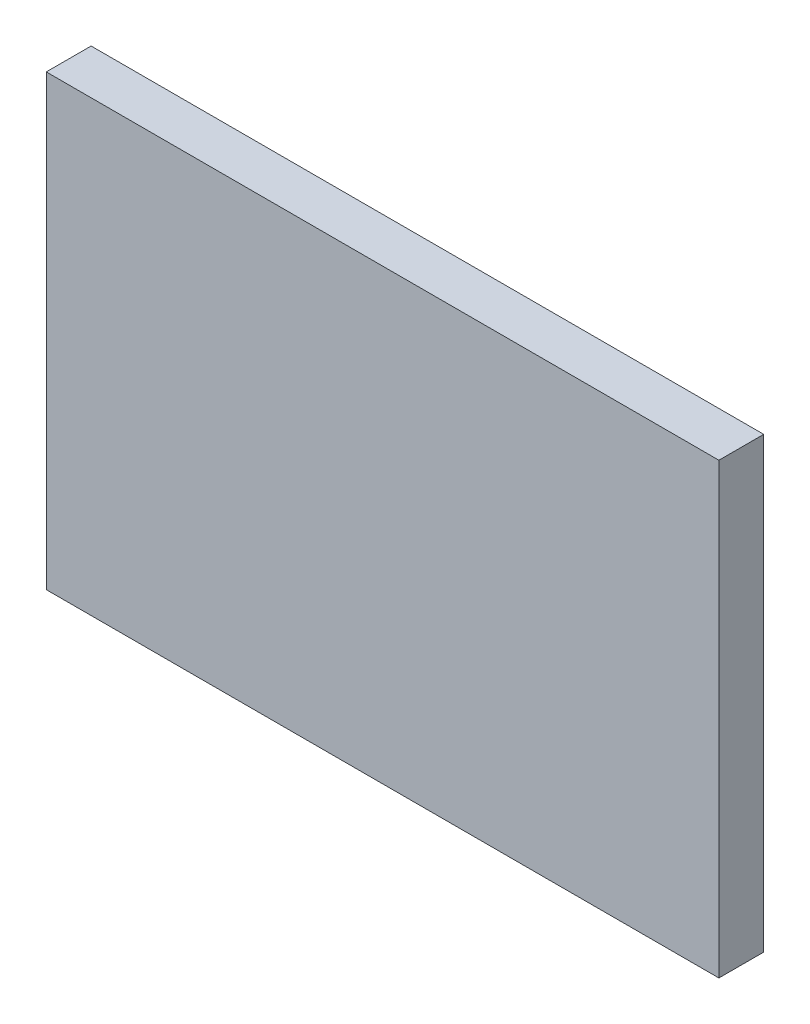
SolidWorks part; units mm, degrees
ref_plane "Ebene vorne" through (0, 0, 0) normal (0, 0, 1) x (1, 0, 0)
ref_plane "Ebene oben" through (0, 0, 0) normal (0, 1, 0) x (1, 0, 0)
ref_plane "Ebene rechts" through (0, 0, 0) normal (1, 0, 0) x (0, 0, -1)
other "Massenmittelpunkt"
sketch "Skizze1" plane through (0, 0, 0) normal (0, 0, 1) x (1, 0, 0)
  line L0 (-15, 10) -> (-15, -10)
  line L1 (-15, -10) -> (15, -10)
  line L2 (15, -10) -> (15, 10)
  line L3 (15, 10) -> (-15, 10)
  line L4 (-15, 0) -> (15, 0) construction
  line L5 (0, 10) -> (0, -10) construction
  point P3 (0, 10)
  point P5 (15, 0)
  point P6 (0, -10)
  point P7 (-15, 0)
  point P12 (0, 0)
  dimension "D1" = 30
  dimension "D2" = 30
  dimension "D3" = 20
  dimension "D4" = 20
  dimension "D5" = 90
ref_axis "Achse1" through (11, 0, 0) along (-1, 0, 0)
ref_plane "Rotation_Plane" through (0, 0, 0) normal (0, 0, -1) x (-1, 0, 0)
ref_plane "Top_Plane" through (0, 0, 2) normal (0, 0, -1) x (-1, 0, 0)
sketch "Skizze2" plane through (0, 0, 2) normal (0, 0, -1) x (-1, 0, 0)
  line L0 (15, 10) -> (15, -10)
  line L1 (15, -10) -> (-15, -10)
  line L2 (-15, -10) -> (-15, 10)
  line L3 (-15, 10) -> (15, 10)
  line L4 (0, 10) -> (0, -10) construction
  line L5 (15, 0) -> (-15, 0) construction
  line L6 (0, 10) -> (0, -10) construction
  line L7 (0, 10) -> (0, -10) construction
  point P0 (0, 0)
  point P6 (0, 10)
  point P7 (-15, 0)
  point P8 (0, -10)
  point P9 (15, 0)
  point P14 (0, 0)
  dimension "D5" = 90
  dimension "D1" = 20
  dimension "D2" = 20
  dimension "D3" = 30
  dimension "D4" = 30
  dimension "D6" = 0
loft "Ausformung2" add profiles "Skizze1", "Skizze2" connector at (-15, -10, 0) connector at (-15, -10, 2)
ref_point "SWASI_Vision_Point_1_T"
ref_point "SWASI_Vision_Point_1_B"
ref_point "SWASI_Vision_Point_2_T"
ref_point "SWASI_Vision_Point_2_B"
ref_point "SWASI_Vision_Point_3_T"
ref_point "SWASI_Vision_Point_3_B"
ref_point "SWASI_Vision_Point_4_T"
ref_point "SWASI_Vision_Point_4_B"
sketch "Skizze3" plane through (0, 0, 2) normal (0, 0, 1) x (1, 0, 0)
  line L0 (-15, 0) -> (15, 0) construction
  line L1 (0, 10) -> (0, -10) construction
  line L3 (-14, -9) -> (14, -9)
  line L4 (15, 10) -> (-15, 10)
  line L5 (-15, 10) -> (-15, -10)
  line L6 (-15, -10) -> (15, -10)
  line L7 (15, -10) -> (15, 10)
  line L8 (15, 10) -> (-15, 10) construction
  line L9 (-15, 10) -> (-15, -10) construction
  line L10 (-15, -10) -> (15, -10) construction
  line L11 (15, -10) -> (15, 10) construction
  line L12 (-14, -9) -> (-14, 9)
  line L13 (-14, 9) -> (14, 9)
  line L14 (14, -9) -> (14, 9)
  line L15 (-14, -9) -> (14, 9) construction
  line L16 (-14, 9) -> (14, -9) construction
  point P8 (0, 0)
  point P9 (0, 0)
  dimension "D2" = 28
  dimension "D3" = 18
  dimension "D1" = 0
ref_point "SWASI_Laser_1_T"
ref_point "SWASI_Laser_2_T"
ref_point "SWASI_Laser_3_T"
ref_point "SWASI_Laser_4_T"
ref_point "SWASI_Gripping_Point"
sketch "Skizze4" plane through (0, 0, 0) normal (0, 0, -1) x (-1, 0, 0)
  line L1 (14, 9) -> (-14, 9)
  line L2 (14, 9) -> (14, -9)
  line L3 (14, -9) -> (-14, -9)
  line L4 (-14, 9) -> (-14, -9)
  line L5 (14, 9) -> (-14, -9) construction
  line L6 (14, -9) -> (-14, 9) construction
  point P0 (0, 0)
  point P2 (0, 0)
  dimension "D1" = 28
  dimension "D2" = 18
ref_point "SWASI_Laser_1_B"
ref_point "SWASI_Laser_2_B"
ref_point "SWASI_Laser_3_B"
ref_point "SWASI_Laser_4_B"
ref_plane "SWASI_Top_Plane" through (0, 0, 2) normal (0, 0, -1) x (-1, 0, 0)
ref_plane "SWASI_Bottom_Plane" through (0, 0, 0) normal (0, 0, -1) x (-1, 0, 0)
ref_axis "SWASI_Bottom_Axis" through (15, -10, 0) along (-1, 0, 0)
ref_axis "SWASI_Top_Axis" through (15, -10, 2) along (-1, 0, 0)
sketch "Axis_Center_B" plane through (0, 0, 0) normal (0, 0, -1) x (-1, 0, 0)
  line L0 (15, -10) -> (-15, -10) construction
  line L1 (15, -10) -> (-15, -10)
  point P2 (0, -10)
sketch "Skizze6" plane through (0, 0, 2) normal (0, 0, 1) x (1, 0, 0)
  line L0 (15, -10) -> (-15, -10) construction
  point P0 (0, -10)
  point P1 (-12.736, 25.2765)
ref_point "SWASI_Axis_Center_B"
ref_point "SWASI_Axis_Center_T"
ref_plane "SWASI_Axis_T_Plane" through (0, -10, 2) normal (-1, 0, 0) x (0, 0, 1)
ref_plane "SWASI_Axis_B_Plane" through (0, -10, 0) normal (-1, 0, 0) x (0, 0, 1)
ref_plane "Bottom_Reference" through (0, 0, 3) normal (0, 0, -1) x (-1, 0, 0)
ref_plane "Top_Reference" through (0, 0, -1) normal (0, 0, 1) x (1, 0, 0)
sketch "Skizze7" plane through (0, 229.1773, 3) normal (0, 0, -1) x (1, 0, 0)
  point P0 (-15, 239.1773)
ref_point "SWASI_Front_Bottom_Reference"
ref_plane "SWASI_Front_Plane_B" through (0, -10, 0) normal (0, 1, 0) x (1, 0, 0.0001)
sketch "Skizze9" plane through (0, 229.1773, -1) normal (0, 0, 1) x (-1, 0, 0)
  point P0 (-15, 239.1773)
ref_point "SWASI_Front_Top_Reference"
ref_plane "SWASI_Front_Plane_T" through (0, -10, 0) normal (0, -1, 0) x (-1, 0, -0.0006)
sketch "Skizze10" plane through (0, 0, 0) normal (0, 0, -1) x (-1, 0, 0)
  line L0 (-17, 12) -> (-17, -8) construction
  line L1 (-17, 12) -> (3, 12) construction
  point P2 (-15, -10)
  point P4 (15, 10)
  dimension "D1" = 20
  dimension "D2" = 20
  dimension "D3" = 2
  dimension "D4" = 2
ref_point "Punkt44"
equation "\"Length_1\" = 20"
equation "\"Length_2\" = 20"
equation "\"Length_3\" = 30"
equation "\"Length_4\" = 30"
equation "\"D1@Skizze1\"=\"Length_3\""
equation "\"D2@Skizze1\"=\"Length_4\""
equation "\"D3@Skizze1\"=\"Length_1\""
equation "\"D4@Skizze1\"=\"Length_2\""
equation "\"Angle_1\"= 90"
equation "\"Angle_2\"= 90"
equation "\"Plane_Angle\" = 0"
equation "\"D5@Skizze1\"=\"Angle_1\""
equation "\"Plane_Distance\"= 1"
equation "\"Length_1_1\" = 20"
equation "\"Length_1_2\" = 20"
equation "\"Length_1_3\" = 30"
equation "\"Length_1_4\" = 30"
equation "\"Angle_3\"= 90"
equation "\"Angle_4\"= 90"
equation "\"D1@Skizze2\"=\"Length_1_1\""
equation "\"D2@Skizze2\"=\"Length_1_2\""
equation "\"D3@Skizze2\"=\"Length_1_3\""
equation "\"D4@Skizze2\"=\"Length_1_4\""
equation "\"D5@Skizze2\"=\"Angle_3\""
equation "\"Angle_Plane_rot\"= 0"
equation "\"D6@Skizze2\"=\"Angle_Plane_rot\""
